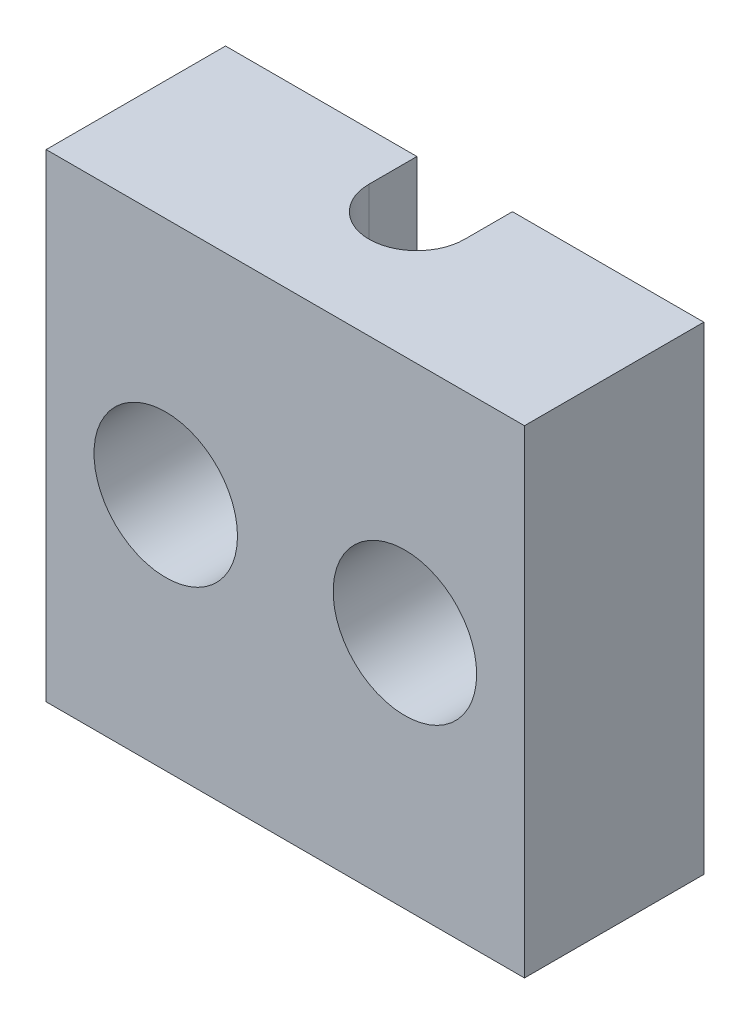
SolidWorks part; units mm, degrees
ref_plane "Front Plane" through (0, 0, 0) normal (0, 0, 1) x (1, 0, 0)
ref_plane "Top Plane" through (0, 0, 0) normal (0, 1, 0) x (1, 0, 0)
ref_plane "Right Plane" through (0, 0, 0) normal (1, 0, 0) x (0, 0, -1)
sketch "Sketch1" plane through (0, 0, 0) normal (0, 0, 1) x (1, 0, 0)
  line L1 (-5.08, 5.08) -> (5.08, 5.08)
  line L2 (-5.08, 5.08) -> (-5.08, -5.08)
  line L3 (-5.08, -5.08) -> (5.08, -5.08)
  line L4 (5.08, 5.08) -> (5.08, -5.08)
  line L5 (-5.08, 5.08) -> (5.08, -5.08) construction
  line L6 (-5.08, -5.08) -> (5.08, 5.08) construction
  point P0 (0, 0)
  dimension "D1" = 10.16
  dimension "D2" = 10.16
extrude "Boss-Extrude1" add sketch "Sketch1" along normal blind 3.81
sketch "Sketch2" plane through (0, 0, 3.81) normal (0, 0, 1) x (1, 0, 0)
  line L0 (-5.08, 5.08) -> (-5.08, -5.08) construction
  line L2 (-5.08, -5.08) -> (5.08, -5.08) construction
  circle A0 centre (2.54, 0) radius 1.524
  circle A1 centre (-2.54, 0) radius 1.524
  dimension "D1" = 3.048
  dimension "D2" = 5.08
  dimension "D3" = 2.54
  dimension "D4" = 5.08
extrude "Cut-Extrude1" cut sketch "Sketch2" against normal up to surface (3.81 mm away) up to face at (0, 0, 0)
sketch "Sketch3" plane through (0, -5.08, 0) normal (0, -1, 0) x (1, 0, 0)
  line L4 (-5.08, 0) -> (5.08, 0) construction
  line L5 (-1.0147, 1.016) -> (-1.0147, 0)
  line L6 (1.0147, 1.016) -> (1.0147, 0)
  line L7 (-1.0147, 0) -> (1.0147, 0)
  circle A0 centre (0, 1.016) radius 1.0147
  line M1 (-5.08, 0) -> (5.08, 0)
  dimension "D1" = 2.0295
  dimension "D2" = 1.016
extrude "Cut-Extrude3" cut sketch "Sketch3" against normal up to surface (10.16 mm away) contours A0 | A0 L5 L6 M1 region at (0.992, -5.08, 0.508) region at (0, -5.08, 1.016) up to face at (0, 5.08, 1.905)
